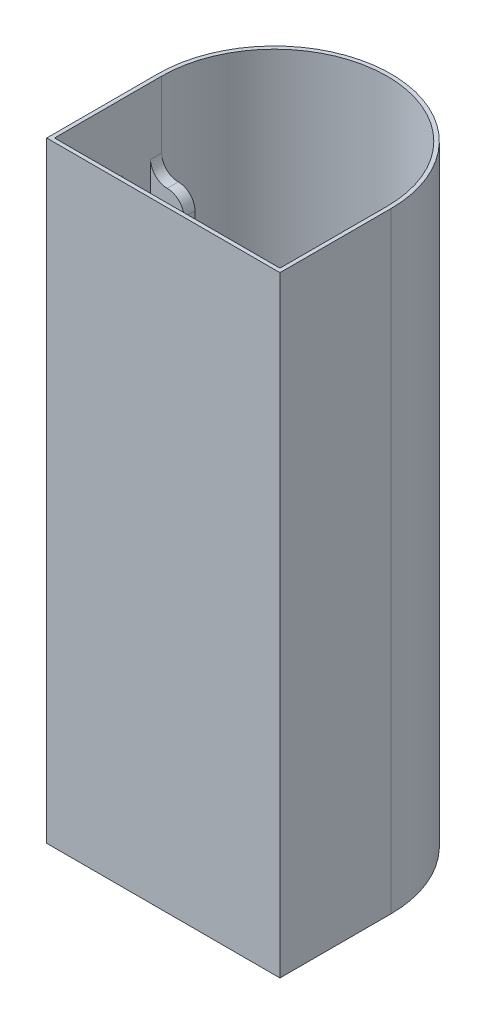
SolidWorks part; units mm, degrees
ref_plane "Front Plane" through (0, 0, 0) normal (0, 0, 1) x (1, 0, 0)
ref_plane "Top Plane" through (0, 0, 0) normal (0, 1, 0) x (1, 0, 0)
ref_plane "Right Plane" through (0, 0, 0) normal (1, 0, 0) x (0, 0, -1)
sketch "Sketch1" plane through (0, 0, 0) normal (0, 1, 0) x (1, 0, 0)
  line L0 (-40.8831, -1.7077) -> (1.1169, -1.7077)
  line L2 (-40.8831, -1.7077) -> (-40.8831, 18.2923)
  line L4 (1.1169, -1.7077) -> (1.1169, 18.2923)
  arc A0 (1.1169, 18.2923) -> (-40.8831, 18.2923) centre (-19.8831, 18.2923) ccw
  dimension "D3" = 21
  dimension "D1" = 42
  dimension "D2" = 20
extrude "Boss-Extrude1" add sketch "Sketch1" along normal blind 110 contours L2 A0 L4 L0
sketch "Sketch2" plane through (0, 110, 0) normal (0, 1, 0) x (1, 0, 0)
  line L5 (-40.1831, 16.2923) -> (-40.1831, 11.2923)
  line L6 (-40.1831, -1.0077) -> (0.4169, -1.0077)
  line L8 (-40.1831, 18.2923) -> (-34.1831, 18.2923)
  line L9 (-34.1831, 18.2923) -> (-34.1831, 16.2923)
  line L10 (-34.1831, 16.2923) -> (-40.1831, 16.2923)
  line L12 (-40.1831, 11.2923) -> (-34.1831, 11.2923)
  line L13 (-34.1831, 11.2923) -> (-34.1831, 9.2923)
  line L14 (-34.1831, 9.2923) -> (-40.1831, 9.2923)
  line L15 (0.4169, 9.2923) -> (0.4169, -1.0077)
  line L16 (-40.1831, 9.2923) -> (-40.1831, -1.0077)
  line L17 (-5.5831, 9.2923) -> (0.4169, 9.2923)
  line L18 (-5.5831, 11.2923) -> (-5.5831, 9.2923)
  line L19 (0.4169, 11.2923) -> (-5.5831, 11.2923)
  line L20 (-5.5831, 16.2923) -> (0.4169, 16.2923)
  line L21 (-5.5831, 18.2923) -> (-5.5831, 16.2923)
  line L22 (0.4169, 18.2923) -> (-5.5831, 18.2923)
  line L23 (-40.8831, -1.7077) -> (1.1169, -1.7077) construction
  line L24 (-40.8831, -1.7077) -> (-40.8831, 18.2923) construction
  line L25 (0.4169, 16.2923) -> (0.4169, 11.2923)
  arc A4 (0.4169, 18.2923) -> (-40.1831, 18.2923) centre (-19.8831, 18.2923) ccw
  point P25 (-19.8831, -1.0077)
  dimension "D13" = 20.3
  dimension "D1" = 6
  dimension "D2" = 2
  dimension "D3" = 5
  dimension "D4" = 2
  dimension "D5" = 6
  dimension "D6" = 0.7
  dimension "D7" = 0.7
  dimension "D8" = 6
  dimension "D9" = 5
  dimension "D10" = 2
  dimension "D11" = 2
  dimension "D12" = 0.7
  dimension "D14" = 6
extrude "Cut-Extrude1" cut sketch "Sketch2" against normal blind 109.3
sketch "Sketch3" plane through (-40.8831, 0, 0) normal (-1, 0, 0) x (0, 0, 1)
  line L0 (1.7077, 110) -> (1.7077, 0) construction
  line L1 (1.7077, 110) -> (-18.2923, 110) construction
  circle A0 centre (-4.9589, 55) radius 3.375
  dimension "D1" = 6.75
  dimension "D2" = 6.6667
  dimension "D3" = 55
extrude "Cut-Extrude2" cut sketch "Sketch3" against normal blind 5
sketch "Sketch4" plane through (0, 110, 0) normal (0, 1, 0) x (1, 0, 0)
  line L0 (-40.1831, -1.0077) -> (0.4169, -1.0077)
  line L1 (0.4169, -1.0077) -> (0.4169, 18.2923)
  line L2 (0.4169, 18.2923) -> (-40.1831, 18.2923)
  line L3 (-40.1831, 18.2923) -> (-40.1831, -1.0077)
extrude "Cut-Extrude3" cut sketch "Sketch4" against normal blind 15
fillet "Fillet1" radius 3 8 edges at (-34.1831, 95, -10.2923) (-40.1831, 95, -10.2923) (-34.1831, 95, -17.2923) (-40.1831, 95, -17.2923) (0.4169, 95, -10.2923) (-5.5831, 95, -10.2923) (-5.5831, 95, -17.2923) (0.4169, 95, -17.2923)
equation "\"Width\"= 42"
equation "\"Depth\"= 20"
equation "\"lenght\"= 110"
equation "\"thick\"= 0.7"
equation "\"D1@Sketch1\"=\"Width\""
equation "\"D3@Sketch1\"=\"Width\"/2"
equation "\"length\"= 110"
equation "\"D1@Boss-Extrude1\"=\"length\""
equation "\"holder lenght\"= 6"
equation "\"holder width\"= 2"
equation "\"holder gap\"= 5"
equation "\"D1@Sketch2\"=\"holder lenght\""
equation "\"D2@Sketch2\"=\"holder width\""
equation "\"D3@Sketch2\"=\"holder gap\""
equation "\"D4@Sketch2\"=\"holder width\""
equation "\"D5@Sketch2\"=\"holder lenght\""
equation "\"D6@Sketch2\"=\"thick\""
equation "\"D7@Sketch2\"=\"thick\""
equation "\"D1@Cut-Extrude1\"=\"length\"-\"thick\""
equation "\"fillet\"= 0.5"
equation "\"D2@Sketch1\"=\"Depth\""
equation "\"D8@Sketch2\"=\"holder lenght\""
equation "\"D9@Sketch2\"=\"holder gap\""
equation "\"D10@Sketch2\"=\"holder width\""
equation "\"D11@Sketch2\"=\"holder width\""
equation "\"hole\"= 6.75"
equation "\"D1@Sketch3\"=\"hole\""
equation "\"D2@Sketch3\"=\"Depth\"/3"
equation "\"D3@Sketch3\"=\"lenght\"/2"
equation "\"D12@Sketch2\"=\"thick\""
equation "\"D13@Sketch2\"=\"Width\"/2-\"thick\""
equation "\"D14@Sketch2\"=\"holder lenght\""
